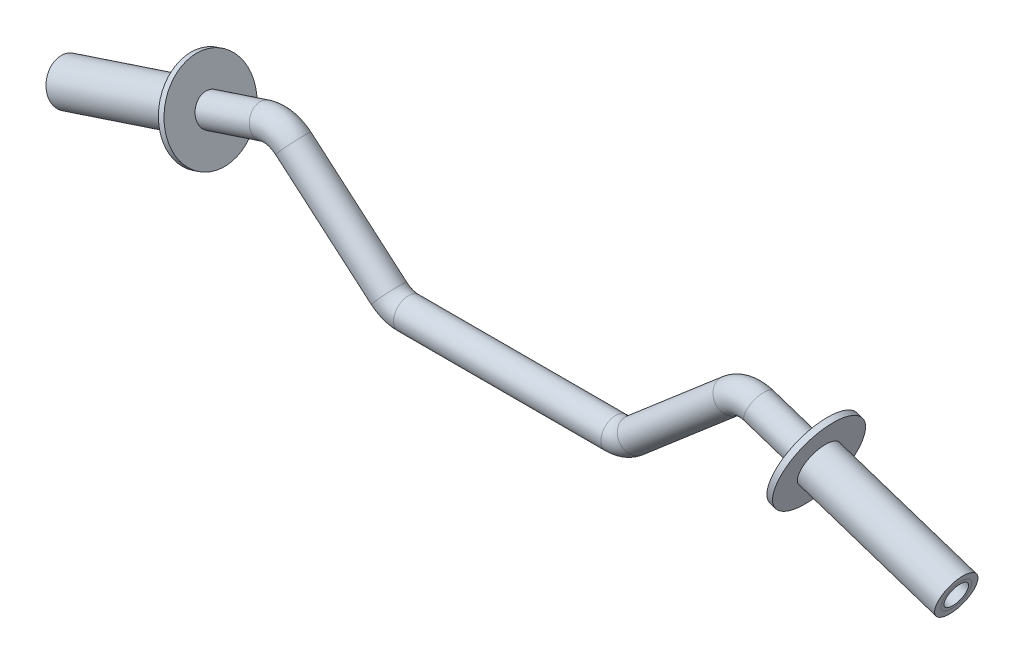
SolidWorks part; units mm, degrees
ref_plane "Front Plane" through (0, 0, 0) normal (0, 0, 1) x (1, 0, 0)
ref_plane "Top Plane" through (0, 0, 0) normal (0, 1, 0) x (1, 0, 0)
ref_plane "Right Plane" through (0, 0, 0) normal (1, 0, 0) x (0, 0, -1)
sketch "Sketch1" plane through (0, 0, 0) normal (0, 0, 1) x (1, 0, 0)
  line L0 (0, 0) -> (70, 0)
  line L1 (83.0168, 4.8157) -> (147.605, 60.1843)
  line L2 (166.8978, 63.9898) -> (300, 20)
  line L3 (0, 0) -> (0, 35.4995) construction
  arc A0 (147.605, 60.1843) -> (166.8978, 63.9898) centre (160.6218, 45) cw
  arc A1 (70, 0) -> (83.0168, 4.8157) centre (70, 20) ccw
  dimension "D1" = 20
  dimension "D2" = 300
  dimension "D3" = 20
  dimension "D4" = 70
  dimension "D5" = 160.6218
  dimension "D6" = 45
sketch "Sketch2" plane through (0, 0, 0) normal (1, 0, 0) x (0, 0, -1)
  circle A0 centre (0, 0) radius 8
  circle A1 centre (0, 0) radius 10
  dimension "D1" = 20
  dimension "D2" = 16
sweep "Sweep1" add profiles "Sketch2" path "Sketch1"
sketch "Sketch3" plane through (143.3013, 55, 0) normal (0, 0, 1) x (-0.866, 0.5, 0)
  line L2 (-155.2349, -38.2467) -> (-55.75, -17.6235)
  line L3 (-17.9702, -9.7918) -> (-155.2349, -38.2467) construction
  line L4 (-55.75, -17.6235) -> (-59.8097, 1.9601)
  line L5 (-59.8097, 1.9601) -> (-63.7264, 1.1482)
  line L6 (-63.7264, 1.1482) -> (-60.4787, -14.5187)
  line L7 (-60.4787, -14.5187) -> (-156.0468, -34.3299)
  line L8 (-156.0468, -34.3299) -> (-155.2349, -38.2467)
  line L9 (-155.2349, -38.2467) -> (-151.1752, -57.8303) construction
  line L10 (-153.2051, -48.0385) -> (-72.4564, -31.2994) construction
  dimension "D1" = 4
  dimension "D2" = 101.6
  dimension "D3" = 4
  dimension "D4" = 20
revolve "Revolve1" add sketch "Sketch3" angle 360 about L10
mirror "Mirror1" about plane through (0, 0, 0) normal (1, 0, 0) of bodies 101 103
combine bodies "Combine1" operation type add bodies to combine 105 101
